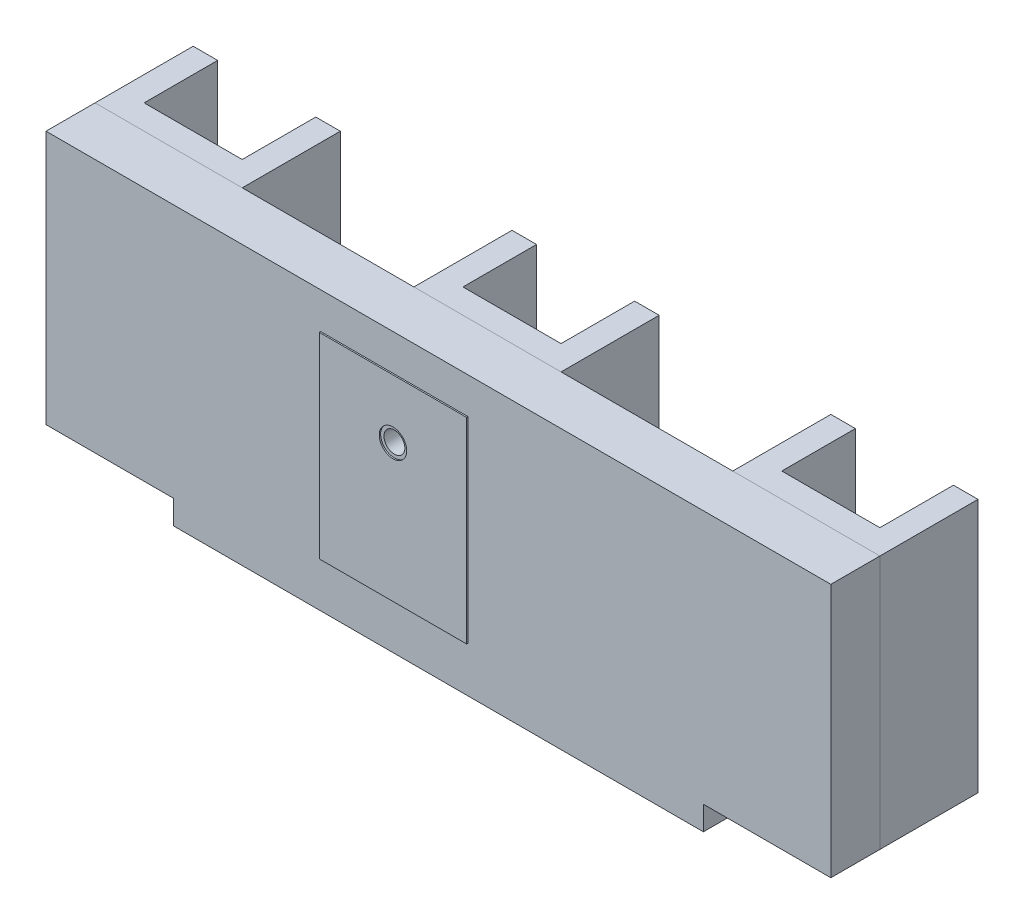
SolidWorks part; units mm, degrees
other "The Block Of Aluminum In Question"
other "SP400-0.007-00-104 Thermal Pad"
ref_plane "Front Plane" through (0, 0, 0) normal (0, 0, 1) x (1, 0, 0)
ref_plane "Top Plane" through (0, 0, 0) normal (0, 1, 0) x (1, 0, 0)
ref_plane "Right Plane" through (0, 0, 0) normal (1, 0, 0) x (0, 0, -1)
sketch "Sketch1" plane through (0, 0, 0) normal (0, 0, 1) x (1, 0, 0)
  line L0 (0, -5.51) -> (0, 38.49) construction
  line L1 (-66.5, -5.51) -> (66.5, -5.51) construction
  line L2 (-66.5, -5.51) -> (-66.5, 38.49) construction
  line L3 (-66.5, 38.49) -> (66.5, 38.49) construction
  line L4 (66.5, -5.51) -> (66.5, 38.49) construction
  line L5 (-50.8, 31.49) -> (50.8, 31.49)
  line L6 (-50.8, 31.49) -> (-50.8, -4.51)
  line L7 (-50.8, -4.51) -> (50.8, -4.51)
  line L8 (50.8, 31.49) -> (50.8, -4.51)
  line L9 (-66.5, 0) -> (66.5, 0) construction
  dimension "D1" = 133
  dimension "D2" = 44
  dimension "D3" = 1
  dimension "D4" = 7
  dimension "D5" = 38.49
  dimension "D6" = 101.6
extrude "Boss-Extrude1" add sketch "Sketch1" along normal blind 6.35
sketch "Sketch2" plane through (0, 0, 6.35) normal (0, 0, 1) x (1, 0, 0)
  point P0 (-5.7, 19.185)
  dimension "D1" = 19.185
  dimension "D2" = 5.7
hole_wizard "Tap Drill for #6-32 Tap2" positions "Sketch2" profile "Sketch3" hole size "#6-32" standard "ANSI Inch" end condition through all
sketch "Sketch3" plane through (-5.7, 19.185, 6.35) normal (1, 0, 0) x (0, -1, 0)
  line L0 (0, 0) -> (0, 6.35)
  line L1 (0, 6.35) -> (1.3525, 6.35)
  line L2 (1.3525, 6.35) -> (1.3525, 0)
  line L5 (1.3525, 0) -> (0, 0)
  line L11 (0, -6.35) -> (0, 107.95) construction
  dimension "Thru Hole Dia." = 2.7051
  dimension "Thru Hole Depth" = 6.35
sketch "Sketch5" plane through (0, 0, 6.35) normal (0, 0, 1) x (1, 0, 0)
  line L0 (50.8, -4.51) -> (50.8, 31.49) construction
  line L1 (50.8, -4.51) -> (34.4, -4.51)
  line L2 (50.8, -4.51) -> (50.8, -1.51)
  line L3 (50.8, -1.51) -> (34.4, -1.51)
  line L4 (34.4, -4.51) -> (34.4, -1.51)
  line L5 (-50.8, -4.51) -> (-34.4, -4.51)
  line L6 (-50.8, -4.51) -> (-50.8, -1.51)
  line L7 (-50.8, -1.51) -> (-34.4, -1.51)
  line L8 (-34.4, -4.51) -> (-34.4, -1.51)
  line L9 (-50.8, -4.51) -> (50.8, -4.51) construction
  line L10 (-50.8, 31.49) -> (-50.8, -4.51) construction
  dimension "D1" = 3
  dimension "D2" = 16.4
extrude "Cut-Extrude1" cut sketch "Sketch5" against normal through all
other "Move Face1" flip direction yes face at (-42.6, -1.51, 3.175) face at (-34.4, -3.01, 3.175) face at (34.4, -3.01, 3.175) face at (42.6, -1.51, 3.175) offset 0.1 parameters "D1"=0.1
sketch "Sketch4" plane through (0, 0, 6.35) normal (0, 0, 1) x (1, 0, 0)
  line L0 (-5.7, 26.805) -> (-5.7, 1.405) construction
  line L1 (-15.225, 1.405) -> (3.825, 1.405)
  line L2 (-15.225, 1.405) -> (-15.225, 26.805)
  line L3 (-15.225, 26.805) -> (3.825, 26.805)
  line L4 (3.825, 1.405) -> (3.825, 26.805)
  circle A0 centre (-5.7, 19.185) radius 1.78
  circle A2 centre (-5.7, 19.185) radius 1.3525 construction
  dimension "D4" = 3.56
  dimension "D1" = 19.05
  dimension "D2" = 25.4
  dimension "D3" = 7.62
extrude "Boss-Extrude2" add sketch "Sketch4" along normal blind 0.178 separate body
sketch "Sketch6" plane through (0, 31.49, 0) normal (0, 1, 0) x (1, 0, 0)
  line L0 (50.8, 12.7) -> (50.8, 0)
  line L1 (50.8, 0) -> (31.75, 0)
  line L2 (31.75, 0) -> (31.75, 12.7)
  line L3 (31.75, 12.7) -> (34.925, 12.7)
  line L4 (34.925, 12.7) -> (34.925, 3.175)
  line L5 (34.925, 3.175) -> (47.625, 3.175)
  line L6 (47.625, 3.175) -> (47.625, 12.7)
  line L7 (47.625, 12.7) -> (50.8, 12.7)
  line L8 (50.8, -6.35) -> (50.8, 0) construction
  line L9 (50.8, 0) -> (-50.8, 0) construction
  line L10 (41.275, 0) -> (41.275, 3.175) construction
  dimension "D1" = 19.05
  dimension "D2" = 12.7
  dimension "D3" = 3.175
extrude "Boss-Extrude3" add sketch "Sketch6" against normal up to surface (32.9 mm away) separate body up to face at (42.55, -1.41, 3.175)
pattern_linear "LPattern1" count 3 spacing 41.275 along (-1, 0, 0) of bodies 106
